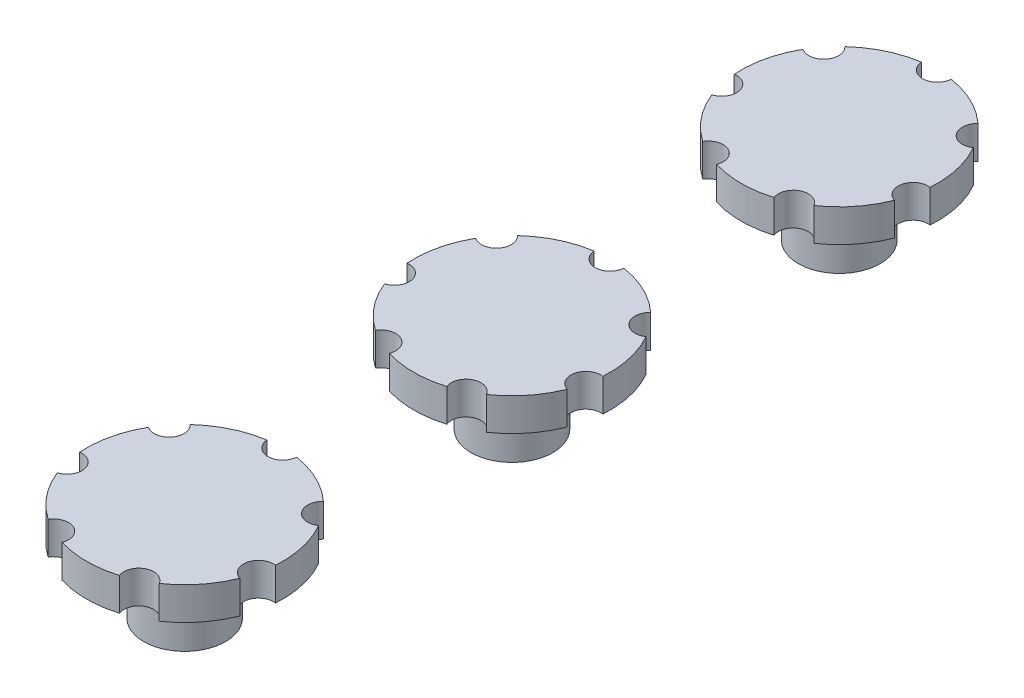
SolidWorks part; units mm, degrees
ref_plane "Front Plane" through (0, 0, 0) normal (0, 0, 1) x (1, 0, 0)
ref_plane "Top Plane" through (0, 0, 0) normal (0, 1, 0) x (1, 0, 0)
ref_plane "Right Plane" through (0, 0, 0) normal (1, 0, 0) x (0, 0, -1)
sketch "Sketch1" plane through (0, 0, 0) normal (0, 1, 0) x (1, 0, 0)
  line L0 (0, 0) -> (0, 6.6879) construction
  circle A0 centre (0, 0) radius 0.6
  circle A1 centre (0, 0) radius 3
  arc A2 (0.4549, 2.9653) -> (-0.4549, 2.9653) centre (0, 3) cw
  arc A3 (2.602, 1.4932) -> (2.0348, 2.2045) centre (2.3455, 1.8705) cw
  arc A4 (2.7897, -1.1033) -> (2.9922, -0.2164) centre (2.9248, -0.6676) cw
  arc A5 (0.8768, -2.869) -> (1.6964, -2.4743) centre (1.3017, -2.7029) cw
  arc A6 (-1.6964, -2.4743) -> (-0.8768, -2.869) centre (-1.3017, -2.7029) cw
  arc A7 (-2.9922, -0.2164) -> (-2.7897, -1.1033) centre (-2.9248, -0.6676) cw
  arc A8 (-2.0348, 2.2045) -> (-2.602, 1.4932) centre (-2.3455, 1.8705) cw
  circle A9 centre (0, 0) radius 1.25
  point P29 (0, 0)
  dimension "D1" = 7
ref_axis "Axis4" [suppressed] through (0, 0, 0) along (0, 0, -1)
extrude "Boss-Extrude1" add sketch "Sketch1" along normal blind 1 from offset 2 contours A1 L0 A9 A2 A8 A7 A6 | L0 A1 A5 A4 A3 A2 A9 | L0 A9 A0 | A9 L0 A0 | A0 L0 | L0 A0 region at (0.8589, 0, -0.8589) region at (0.3676, 0, -2.6033) region at (0.4123, 0, -0.4123)
extrude "Boss-Extrude2" add sketch "Sketch1<28>" along normal blind 2 contours A9 L0 A0 | L0 A9 A0 region at (0.8589, 0, -0.8589)
sketch "Sketch1<28>" plane through (0, 0, 0) normal (0, 1, 0) x (1, 0, 0) same geometry as "Sketch1"
pattern_linear "LPattern1" count 3 spacing 10 along (0, 0, -1) of bodies 197
